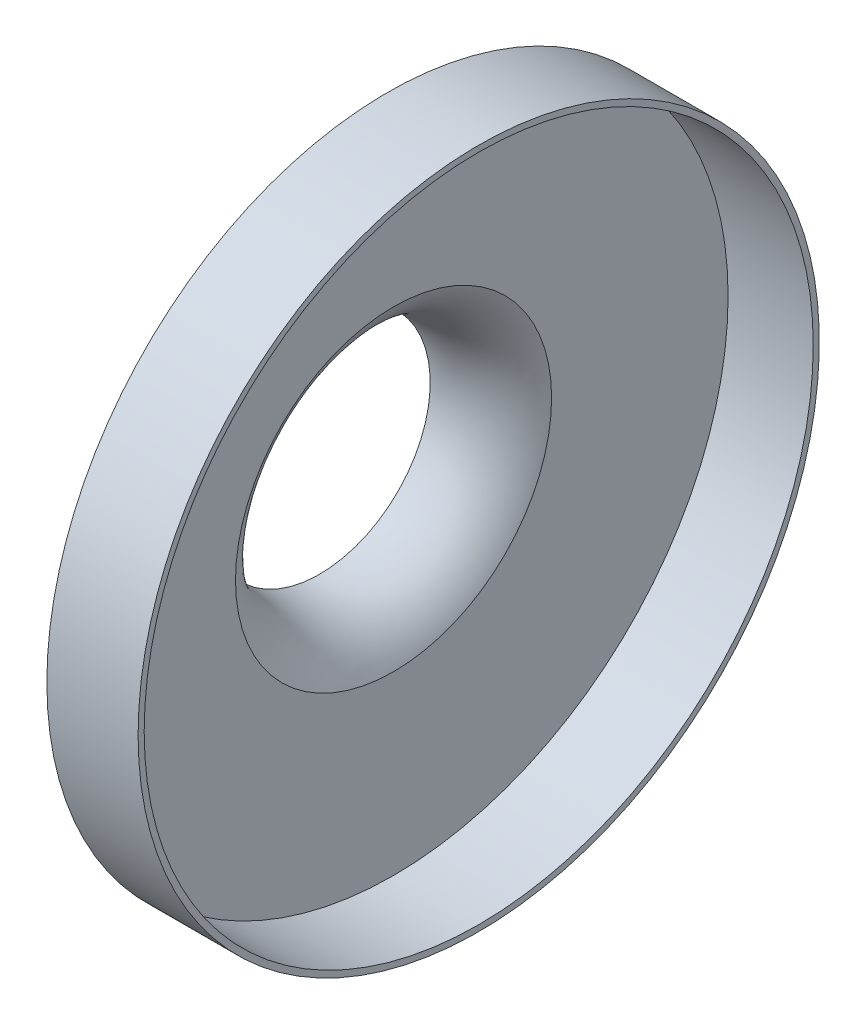
SolidWorks part; units mm, degrees
ref_plane "Front Plane" through (0, 0, 0) normal (0, 0, 1) x (1, 0, 0)
ref_plane "Top Plane" through (0, 0, 0) normal (0, 1, 0) x (1, 0, 0)
ref_plane "Right Plane" through (0, 0, 0) normal (1, 0, 0) x (0, 0, -1)
sketch "Sketch1" plane through (0, 0, 0) normal (0, 0, 1) x (1, 0, 0)
  line L0 (15.4464, 33.0001) -> (15.4464, 69.85)
  line L1 (0, 33.0001) -> (24.7431, 33.0001) construction
  line L2 (15.4464, 69.85) -> (33.2264, 69.85)
  line L3 (0, 0) -> (54.525, 0) construction
  line L4 (14.1764, 33.2836) -> (14.1764, 71.12)
  line L5 (14.1764, 71.12) -> (33.2264, 71.12)
  line L6 (33.2264, 71.12) -> (33.2264, 69.85)
  line L7 (0, 24.37) -> (0, 23.1)
  circle A0 centre (0, 40.1) radius 17 construction
  arc A1 (0, 23.1) -> (15.4464, 33.0001) centre (0, 40.1) ccw
  arc A2 (0, 24.37) -> (14.1764, 33.2836) centre (0, 40.1) ccw
  point P0 (0, 23.1)
  dimension "D3" = 17
  dimension "D1" = 33.0001
  dimension "D2" = 23.1
  dimension "D4" = 33.9999
  dimension "D5" = 69.85
  dimension "D6" = 17.78
  dimension "D7" = 1.27
revolve "Revolve1" add sketch "Sketch1" angle 360 about L3
